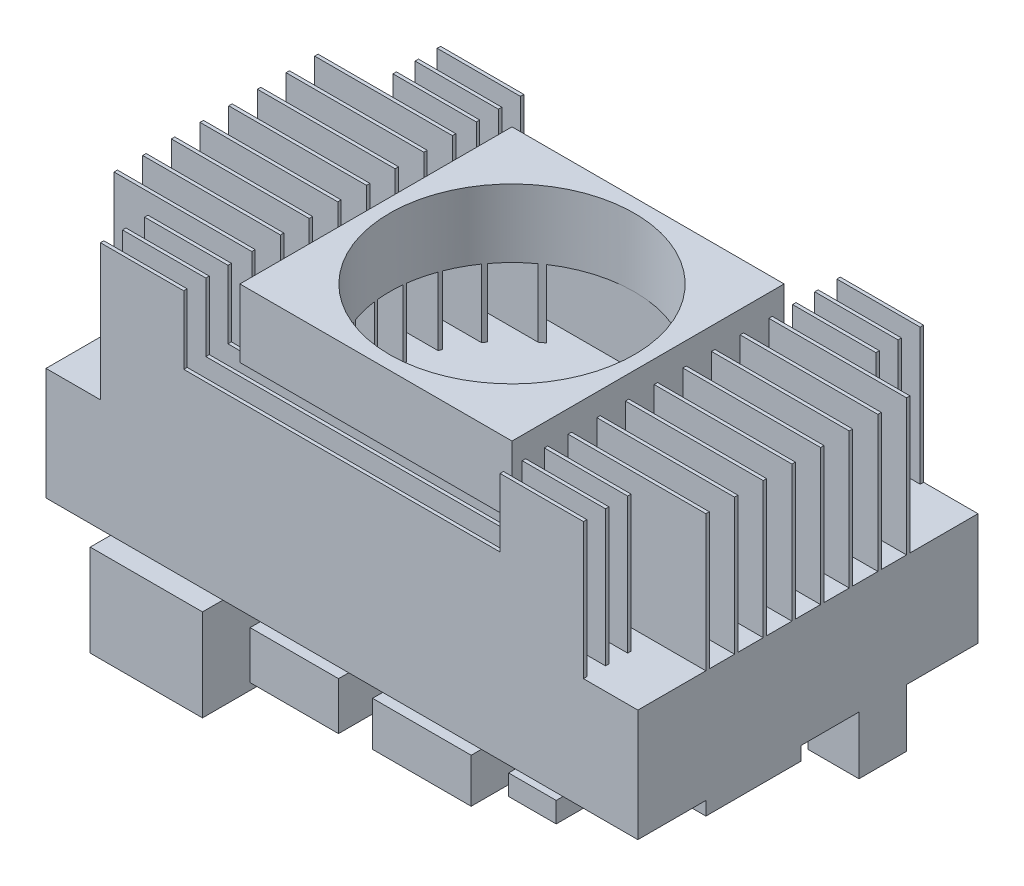
SolidWorks part; units mm, degrees
ref_plane "前视基准面" through (0, 0, 0) normal (0, 0, 1) x (1, 0, 0)
ref_plane "上视基准面" through (0, 0, 0) normal (0, 1, 0) x (1, 0, 0)
ref_plane "右视基准面" through (0, 0, 0) normal (1, 0, 0) x (0, 0, -1)
sketch "Front" plane through (0, 0, 0) normal (0, 0, 1) x (1, 0, 0)
  line L0 (0, 26) -> (0, -26) construction
  line L1 (-43.5, 26) -> (43.5, 26)
  line L2 (-43.5, 26) -> (-43.5, -26)
  line L3 (-43.5, -26) -> (43.5, -26)
  line L4 (43.5, 26) -> (43.5, -26)
  line L5 (-43.5, 0) -> (43.5, 0) construction
  dimension "D1" = 87
  dimension "D2" = 52
extrude "凸台-拉伸1" add sketch "Front" against normal blind 50
sketch "Up" plane through (0, 26, 0) normal (0, 1, 0) x (1, 0, 0)
  line L0 (-20, 25) -> (20, 25) construction
  line L1 (-20, 45) -> (20, 45)
  line L2 (-20, 45) -> (-20, 5)
  line L3 (-20, 5) -> (20, 5)
  line L4 (20, 45) -> (20, 5)
  line L5 (0, 45) -> (0, 5) construction
  line L6 (-43.5, 0) -> (43.5, 0) construction
  line L7 (-43.5, 50) -> (43.5, 50) construction
  line L8 (-43.5, 50) -> (-43.5, 0)
  line L9 (-43.5, 0) -> (43.5, 0)
  line L10 (43.5, 50) -> (43.5, 0)
  line L11 (-43.5, 25) -> (43.5, 25) construction
  line L12 (0, 50) -> (0, 0) construction
  line L13 (-39.5, 46) -> (-43.5, 46) construction
  line L14 (-39.5, 46) -> (-39.5, 50) construction
  line L15 (-39.5, 4) -> (39.5, 4) construction
  line L16 (39.5, 4) -> (39.5, 46) construction
  line L17 (39.5, 46) -> (43.5, 46) construction
  line L18 (39.5, 46) -> (39.5, 50) construction
  line L19 (-39.5, 46) -> (-39.5, 4) construction
  line L20 (39.5, 46) -> (-39.5, 46) construction
  line L21 (-39.5, 4) -> (-39.5, 0) construction
  line L22 (-39.5, 4) -> (-43.5, 4) construction
  line L23 (-23.25, 50) -> (-23.25, 0)
  line L24 (23.25, 50) -> (23.25, 0)
  line L25 (43.5, 42) -> (35.5, 42)
  line L26 (-43.5, 50) -> (-35.5, 50)
  line L27 (-43.5, 50) -> (-43.5, 42)
  line L28 (-43.5, 42) -> (-35.5, 42)
  line L29 (-35.5, 50) -> (-35.5, 42)
  line L30 (35.5, 50) -> (35.5, 42)
  line L31 (43.5, 50) -> (35.5, 50)
  line L32 (43.5, 50) -> (43.5, 42)
  line L33 (43.5, 0) -> (35.5, 0)
  line L34 (35.5, 0) -> (35.5, 8)
  line L35 (43.5, 8) -> (35.5, 8)
  line L36 (43.5, 0) -> (43.5, 8)
  line L37 (-43.5, 8) -> (-35.5, 8)
  line L38 (-35.5, 0) -> (-35.5, 8)
  line L39 (-43.5, 0) -> (-35.5, 0)
  line L40 (-43.5, 0) -> (-43.5, 8)
  circle A0 centre (-39.5, 46) radius 2.5
  circle A1 centre (39.5, 46) radius 2.5
  circle A2 centre (39.5, 4) radius 2.5
  circle A3 centre (-39.5, 4) radius 2.5
  circle A4 centre (0, 25) radius 18
  line M5 (-43.5, 0) -> (43.5, 0)
  line M6 (43.5, 0) -> (43.5, 50)
  line M7 (43.5, 50) -> (-43.5, 50)
  line M8 (-43.5, 50) -> (-43.5, 0)
  dimension "D2" = 2
  dimension "D5" = 5
  dimension "D11" = 36
  dimension "D1" = 40
  dimension "D3" = 2
  dimension "D4" = 50
  dimension "D6" = 79
  dimension "D7" = 42
  dimension "D8" = 87
  dimension "D9" = 4
  dimension "D10" = 4
  dimension "D12" = 23.25
  dimension "D13" = 8
  dimension "D14" = 8
extrude "切除-拉伸1" cut sketch "Up" against normal blind 20 contours L29 L28 A0 M7 M8 | A0 | L38 L37 A3 M5 M8 | A3 | A2 | L35 L34 L9 A2 M6 | A4 | L30 L25 L10 A1 M7 | A1 region at (-39.5, 26, -49.8869) region at (-39.5, 26, -7.8869) region at (39.5, 26, -49.8869) region at (35.6131, 26, -4) region at (-39.5, 26, -46) region at (39.5, 26, -46) region at (39.5, 26, -4) region at (-39.5, 26, -4) region at (0, 26, -25)
sketch "Tubes" plane through (-43.5, 0, 0) normal (-1, 0, 0) x (0, 0, 1)
  line L0 (-25, 26) -> (-25, 6) construction
  line L1 (-50, 26) -> (0, 26)
  line L2 (-50, 26) -> (-50, 6)
  line L3 (-50, 6) -> (0, 6)
  line L4 (0, 26) -> (0, 6)
  line L5 (-10.5, 26) -> (-10.5, 6)
  line L6 (-10, 26) -> (-10, 6)
  line L7 (-14.2143, 26) -> (-14.2143, 6)
  line L8 (-14.7143, 26) -> (-14.7143, 6)
  line L9 (-18.4286, 26) -> (-18.4286, 6)
  line L10 (-18.9286, 26) -> (-18.9286, 6)
  line L11 (-22.6429, 26) -> (-22.6429, 6)
  line L12 (-23.1429, 26) -> (-23.1429, 6)
  line L13 (-26.8571, 26) -> (-26.8571, 6)
  line L14 (-27.3571, 26) -> (-27.3571, 6)
  line L15 (-25, 16) -> (-10, 16) construction
  line L16 (-25, 16) -> (-40, 16) construction
  line L17 (0, 26) -> (0, 6)
  line L18 (-0.5, 26) -> (-0.5, 6)
  line L19 (-3.75, 26) -> (-3.75, 6)
  line L20 (-3.25, 26) -> (-3.25, 6)
  line L21 (-7, 26) -> (-7, 6)
  line L22 (-6.5, 26) -> (-6.5, 6)
  line L23 (-49.5, 26) -> (-49.5, 6)
  line L24 (-46.75, 26) -> (-46.75, 6)
  line L25 (-31.0714, 26) -> (-31.0714, 6)
  line L26 (-31.5714, 26) -> (-31.5714, 6)
  line L27 (-35.2857, 26) -> (-35.2857, 6)
  line L28 (-35.7857, 26) -> (-35.7857, 6)
  line L29 (-39.5, 26) -> (-39.5, 6)
  line L30 (-40, 26) -> (-40, 6)
  line L31 (-46.25, 26) -> (-46.25, 6)
  line L32 (-43.5, 26) -> (-43.5, 6)
  line L33 (-43, 26) -> (-43, 6)
  line M1 (-42, 26) -> (-42, 6)
  line M2 (-42, 6) -> (-50, 6)
  line M6 (0, 6) -> (-8, 6)
  line M7 (-8, 6) -> (-8, 26)
  line M8 (-8, 26) -> (-42, 26)
  dimension "D1" = 0.5
  dimension "D2" = 30
  dimension "D4" = 0.5
  dimension "D5" = 3
  dimension "D6" = 7
  dimension "D3" = 8
extrude "切除-拉伸2" cut sketch "Tubes" against normal through all both and the other way through all contours L24 L1 L23 L3 | L32 L1 L31 L3 | L1 L33 M2 M1 | L30 L1 L3 M1 | L1 L29 L3 L28 | L1 L27 L3 L26 | L1 L25 L3 L14 | L1 L13 L3 L12 | L1 L11 L3 L10 | L1 L9 L3 L8 | L1 L7 L3 L5 | L6 L3 M8 M7 | L21 L1 L3 M7 | L1 L22 L19 M6 | L1 L20 L3 L18 region at (-43.5, 16, -48.125) region at (-43.5, 16, -44.875) region at (-43.5, 16, -42.5) region at (-43.5, 16, -41) region at (-43.5, 16, -37.6429) region at (-43.5, 16, -33.4286) region at (-43.5, 16, -29.2143) region at (-43.5, 16, -25) region at (-43.5, 16, -20.7857) region at (-43.5, 16, -16.5714) region at (-43.5, 16, -12.3571) region at (-43.5, 16, -9) region at (-43.5, 16, -7.5) region at (-43.5, 16, -5.125) region at (-43.5, 16, -1.875)
extrude "切除-拉伸3" cut sketch "Up<3>" against normal blind 10 contours L24 L23 L9 L1 L4 L3 L2 M7 region at (0, 26, -49.3172)
sketch "Up<3>" plane through (0, 26, 0) normal (0, 1, 0) x (1, 0, 0) same geometry as "Up"
extrude "凸台-拉伸2" add sketch "Up<4>" against normal blind 10 contours L4 L1 L2 L3 A4 region at (0, 26, -44.4343)
sketch "Up<4>" plane through (0, 26, 0) normal (0, 1, 0) x (1, 0, 0) same geometry as "Up"
sketch "Interfaces" plane through (0, 0, 0) normal (0, 0, 1) x (1, 0, 0)
  line L0 (-43.5, 26) -> (-43.5, -26) construction
  line L1 (-43.5, -10.5) -> (43.5, -10.5)
  line L2 (43.5, 26) -> (43.5, -26) construction
  line L3 (-43.5, 26) -> (43.5, 26) construction
  line L4 (-43.5, -9) -> (43.5, -9)
  line L5 (-34, -10.5) -> (-17.5, -10.5)
  line L6 (-34, -10.5) -> (-34, -24)
  line L7 (-34, -24) -> (-17.5, -24)
  line L8 (-17.5, -10.5) -> (-17.5, -24)
  line L9 (-12, -10.5) -> (1, -10.5)
  line L10 (-12, -10.5) -> (-12, -17.5)
  line L11 (-12, -17.5) -> (1, -17.5)
  line L12 (1, -10.5) -> (1, -17.5)
  line L13 (6, -10.5) -> (20.5, -10.5)
  line L14 (6, -10.5) -> (6, -17)
  line L15 (6, -17) -> (20.5, -17)
  line L16 (20.5, -10.5) -> (20.5, -17)
  line L17 (25.5, -10.5) -> (32.5, -10.5)
  line L18 (25.5, -10.5) -> (25.5, -13.5)
  line L19 (25.5, -13.5) -> (32.5, -13.5)
  line L20 (32.5, -10.5) -> (32.5, -13.5)
  line L21 (-43.5, 6) -> (-35.5, 6) construction
  line L23 (-43.5, -10.5) -> (43.5, -10.5)
  line L24 (-43.5, -10.5) -> (-43.5, -26)
  line L25 (-43.5, -26) -> (43.5, -26)
  line L26 (43.5, -10.5) -> (43.5, -26)
  dimension "D1" = 36.5
  dimension "D2" = 16.5
  dimension "D3" = 13.5
  dimension "D4" = 9.5
  dimension "D5" = 5.5
  dimension "D6" = 7
  dimension "D7" = 13
  dimension "D8" = 14.5
  dimension "D9" = 6.5
  dimension "D10" = 5
  dimension "D11" = 7
  dimension "D12" = 3
  dimension "D13" = 5
  dimension "D14" = 1.5
  dimension "D15" = 16.5
extrude "切除-拉伸4" cut sketch "Interfaces" against normal through all contours L24 L23 L26 L25
extrude "凸台-拉伸3" add sketch "Interfaces<3>" against normal blind 30 and the other way blind 3 contours L8 L1 L6 L7 region at (-25.75, -17.25, 0)
sketch "Interfaces<3>" plane through (0, 0, 0) normal (0, 0, 1) x (1, 0, 0) same geometry as "Interfaces"
extrude "凸台-拉伸4" add sketch "Interfaces<4>" against normal blind 15 and the other way blind 1.5 contours L12 L1 L10 L11 region at (-5.5, -14, 0)
sketch "Interfaces<4>" plane through (0, 0, 0) normal (0, 0, 1) x (1, 0, 0) same geometry as "Interfaces"
extrude "凸台-拉伸5" add sketch "Interfaces<5>" against normal blind 9.5 and the other way blind 1.5 contours L16 L1 L14 L15 region at (13.25, -13.75, 0)
sketch "Interfaces<5>" plane through (0, 0, 0) normal (0, 0, 1) x (1, 0, 0) same geometry as "Interfaces"
extrude "凸台-拉伸6" add sketch "Interfaces<6>" against normal blind 3.5 and the other way blind 1 contours L20 L1 L18 L19 region at (29, -12, 0)
sketch "Interfaces<6>" plane through (0, 0, 0) normal (0, 0, 1) x (1, 0, 0) same geometry as "Interfaces"
sketch "草图5" plane through (0, -10.5, 0) normal (0, -1, 0) x (1, 0, 0)
  line L0 (-39, -9) -> (-39, -9.5)
  line L1 (-41.5, -9) -> (-41, -9)
  line L2 (-41.5, -9) -> (-41.5, -9.5)
  line L3 (-41.5, -9.5) -> (-41, -9.5)
  line L4 (-41, -9) -> (-41, -9.5)
  line L5 (-43.5, 0) -> (43.5, 0)
  line L6 (-43.5, 0) -> (-43.5, -50)
  line L7 (-43.5, -50) -> (43.5, -50)
  line L8 (43.5, 0) -> (43.5, -50)
  line L9 (-39, -9) -> (-38.5, -9)
  line L10 (-38.5, -9) -> (-38.5, -9.5)
  line L11 (-39, -9.5) -> (-38.5, -9.5)
  line L12 (-41.5, -11.5) -> (-41.5, -12)
  line L13 (-41.5, -11.5) -> (-41, -11.5)
  line L14 (-41, -11.5) -> (-41, -12)
  line L15 (-41.5, -12) -> (-41, -12)
  line L16 (-39, -11.5) -> (-39, -12)
  line L17 (-39, -11.5) -> (-38.5, -11.5)
  line L18 (-38.5, -11.5) -> (-38.5, -12)
  line L19 (-39, -12) -> (-38.5, -12)
  line L20 (-41.5, -14) -> (-41.5, -14.5)
  line L21 (-41.5, -14) -> (-41, -14)
  line L22 (-41, -14) -> (-41, -14.5)
  line L23 (-41.5, -14.5) -> (-41, -14.5)
  line L24 (-39, -14) -> (-39, -14.5)
  line L25 (-39, -14) -> (-38.5, -14)
  line L26 (-38.5, -14) -> (-38.5, -14.5)
  line L27 (-39, -14.5) -> (-38.5, -14.5)
  line L28 (-41.5, -16.5) -> (-41.5, -17)
  line L29 (-41.5, -16.5) -> (-41, -16.5)
  line L30 (-41, -16.5) -> (-41, -17)
  line L31 (-41.5, -17) -> (-41, -17)
  line L32 (-39, -16.5) -> (-39, -17)
  line L33 (-39, -16.5) -> (-38.5, -16.5)
  line L34 (-38.5, -16.5) -> (-38.5, -17)
  line L35 (-39, -17) -> (-38.5, -17)
  line L36 (-41.5, -19) -> (-41.5, -19.5)
  line L37 (-41.5, -19) -> (-41, -19)
  line L38 (-41, -19) -> (-41, -19.5)
  line L39 (-41.5, -19.5) -> (-41, -19.5)
  line L40 (-39, -19) -> (-39, -19.5)
  line L41 (-39, -19) -> (-38.5, -19)
  line L42 (-38.5, -19) -> (-38.5, -19.5)
  line L43 (-39, -19.5) -> (-38.5, -19.5)
  line L44 (-41.5, -21.5) -> (-41.5, -22)
  line L45 (-41.5, -21.5) -> (-41, -21.5)
  line L46 (-41, -21.5) -> (-41, -22)
  line L47 (-41.5, -22) -> (-41, -22)
  line L48 (-39, -21.5) -> (-39, -22)
  line L49 (-39, -21.5) -> (-38.5, -21.5)
  line L50 (-38.5, -21.5) -> (-38.5, -22)
  line L51 (-39, -22) -> (-38.5, -22)
  line L52 (-41.5, -24) -> (-41.5, -24.5)
  line L53 (-41.5, -24) -> (-41, -24)
  line L54 (-41, -24) -> (-41, -24.5)
  line L55 (-41.5, -24.5) -> (-41, -24.5)
  line L56 (-39, -24) -> (-39, -24.5)
  line L57 (-39, -24) -> (-38.5, -24)
  line L58 (-38.5, -24) -> (-38.5, -24.5)
  line L59 (-39, -24.5) -> (-38.5, -24.5)
  line L60 (-41.5, -26.5) -> (-41.5, -27)
  line L61 (-41.5, -26.5) -> (-41, -26.5)
  line L62 (-41, -26.5) -> (-41, -27)
  line L63 (-41.5, -27) -> (-41, -27)
  line L64 (-39, -26.5) -> (-39, -27)
  line L65 (-39, -26.5) -> (-38.5, -26.5)
  line L66 (-38.5, -26.5) -> (-38.5, -27)
  line L67 (-39, -27) -> (-38.5, -27)
  line L68 (-41.5, -29) -> (-41.5, -29.5)
  line L69 (-41.5, -29) -> (-41, -29)
  line L70 (-41, -29) -> (-41, -29.5)
  line L71 (-41.5, -29.5) -> (-41, -29.5)
  line L72 (-39, -29) -> (-39, -29.5)
  line L73 (-39, -29) -> (-38.5, -29)
  line L74 (-38.5, -29) -> (-38.5, -29.5)
  line L75 (-39, -29.5) -> (-38.5, -29.5)
  line L76 (-41.5, -31.5) -> (-41.5, -32)
  line L77 (-41.5, -31.5) -> (-41, -31.5)
  line L78 (-41, -31.5) -> (-41, -32)
  line L79 (-41.5, -32) -> (-41, -32)
  line L80 (-39, -31.5) -> (-39, -32)
  line L81 (-39, -31.5) -> (-38.5, -31.5)
  line L82 (-38.5, -31.5) -> (-38.5, -32)
  line L83 (-39, -32) -> (-38.5, -32)
  line L85 (28.5, -10) -> (43.5, -10)
  line L86 (28.5, -10) -> (28.5, -24)
  line L87 (28.5, -24) -> (43.5, -24)
  line L88 (43.5, -10) -> (43.5, -24)
  line L89 (36, -32.5) -> (43.5, -32.5)
  line L90 (36, -32.5) -> (36, -39.5)
  line L91 (36, -39.5) -> (43.5, -39.5)
  line L92 (43.5, -32.5) -> (43.5, -39.5)
  dimension "D1" = 0.5
  dimension "D2" = 0.5
  dimension "D3" = 2
  dimension "D4" = 9
  dimension "D7" = 2.5
  dimension "D8" = 2.5
  dimension "D9" = 15
  dimension "D10" = 14
  dimension "D11" = 10
  dimension "D12" = 7.5
  dimension "D13" = 7
  dimension "D14" = 10.5
  dimension "D5" = 2
  dimension "D6" = 10
extrude "凸台-拉伸7" add sketch "草图5" along normal blind 2 contours L86 L85 L88 L87
extrude "凸台-拉伸8" add sketch "草图5<3>" along normal blind 8.5 contours L90 L91 L8 L89 | L32 L35 L34 L33 | L28 L31 L30 L29 | L24 L27 L26 L25 | L20 L23 L22 L21 | L16 L19 L18 L17 | L12 L15 L14 L13 | L4 L1 L2 L3 | L80 L83 L82 L81 | L76 L79 L78 L77 | L68 L71 L70 L69 | L72 L75 L74 L73 | L64 L67 L66 L65 | L60 L63 L62 L61 | L56 L59 L58 L57 | L52 L55 L54 L53 | L44 L47 L46 L45 | L48 L51 L50 L49 | L40 L43 L42 L41 | L36 L39 L38 L37 | L0 L11 L10 L9 region at (-41.25, -10.5, -9.25) region at (39.75, -10.5, -36) region at (-41.25, -10.5, -11.75) region at (-38.75, -10.5, -11.75) region at (-41.25, -10.5, -14.25) region at (-38.75, -10.5, -14.25) region at (-41.25, -10.5, -16.75) region at (-38.75, -10.5, -16.75)
sketch "草图5<3>" plane through (0, -10.5, 0) normal (0, -1, 0) x (1, 0, 0) same geometry as "草图5"
